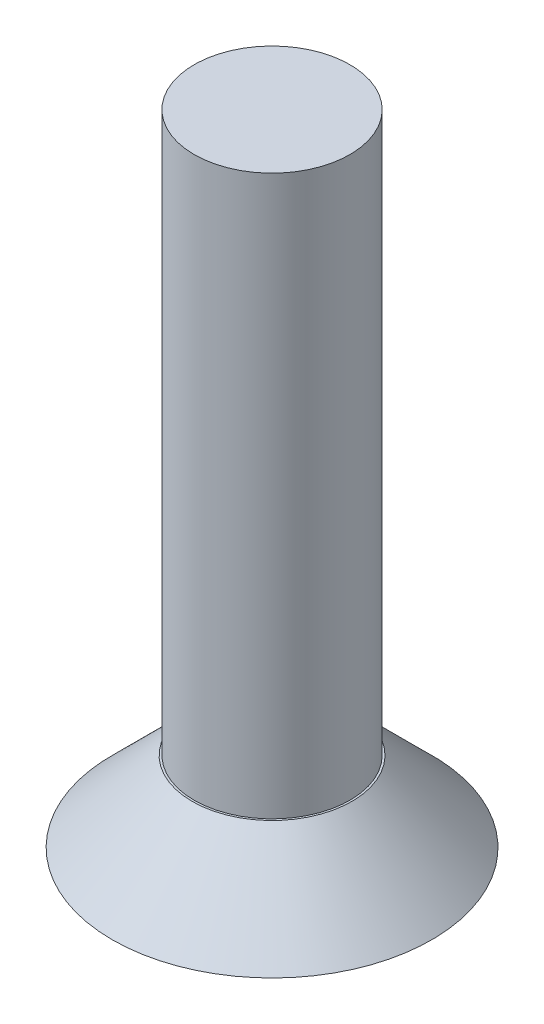
SolidWorks part; units mm, degrees
material "Plain Carbon Steel"
ref_plane "Front Plane" through (0, 0, 0) normal (0, 0, 1) x (1, 0, 0)
ref_plane "Top Plane" through (0, 0, 0) normal (0, 1, 0) x (1, 0, 0)
ref_plane "Right Plane" through (0, 0, 0) normal (1, 0, 0) x (0, 0, -1)
sketch "Sketch1" plane through (0, 0, 0) normal (0, 1, 0) x (1, 0, 0)
  circle A0 centre (0, 0) radius 4
  dimension "D1" = 8
extrude "Boss-Extrude1" add sketch "Sketch1" along normal blind 2
sketch "Sketch2" plane through (0, 2, 0) normal (0, 1, 0) x (1, 0, 0)
  circle A0 centre (0, 0) radius 1.95
  dimension "D1" = 3.9
extrude "Boss-Extrude2" add sketch "Sketch2" along normal blind 14
chamfer "Chamfer1" distance 2 angle 45 1 edges at (0, 2, 4)
sketch "Sketch3" plane through (0, 0, 0) normal (0, -1, 0) x (1, 0, 0)
  line L1 (0, -1.6625) -> (1.4397, -0.8312)
  line L2 (1.4397, -0.8312) -> (1.4397, 0.8312)
  line L3 (1.4397, 0.8312) -> (0, 1.6625)
  line L4 (0, 1.6625) -> (-1.4397, 0.8312)
  line L5 (-1.4397, 0.8312) -> (-1.4397, -0.8312)
  line L6 (-1.4397, -0.8312) -> (0, -1.6625)
  circle A0 centre (0, 0) radius 1.4397 construction
extrude "Cut-Extrude1" cut sketch "Sketch3" against normal blind 1.5
